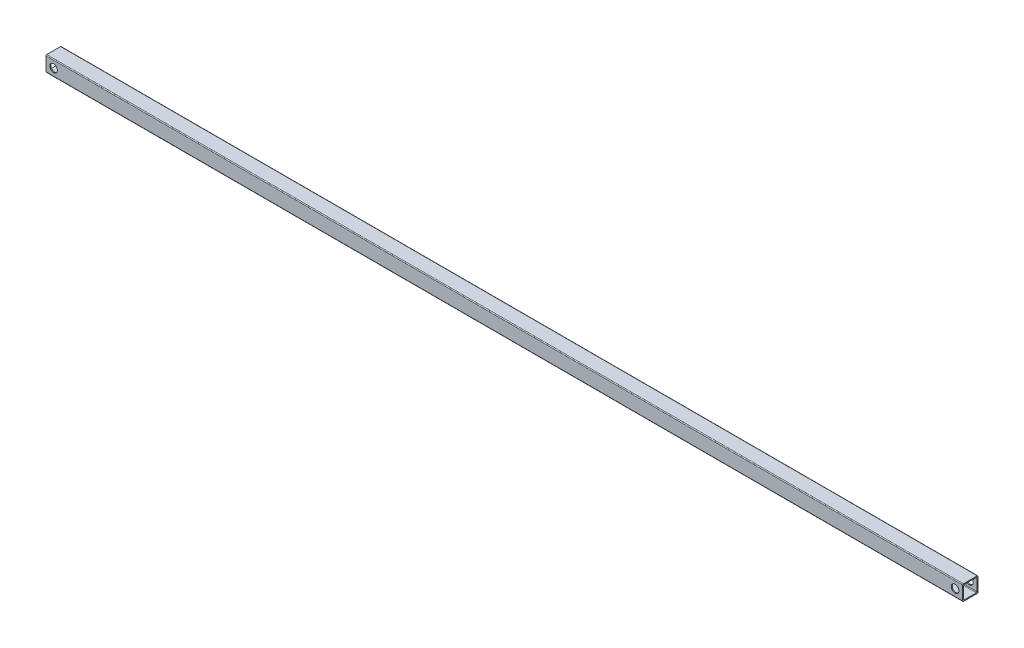
SolidWorks part; units mm, degrees
ref_plane "Front" through (0, 0, 0) normal (0, 0, 1) x (1, 0, 0)
ref_plane "Top" through (0, 0, 0) normal (0, 1, 0) x (1, 0, 0)
ref_plane "Right" through (0, 0, 0) normal (1, 0, 0) x (0, 0, -1)
sketch "Sketch1" plane through (0, 0, 0) normal (1, 0, 0) x (0, 0, -1)
  line L0 (-11.049, 0) -> (-12.7, 0) construction
  line L1 (11.43, -12.7) -> (-11.43, -12.7) construction
  line L2 (12.7, -11.43) -> (12.7, 11.43) construction
  line L3 (11.43, 12.7) -> (-11.43, 12.7) construction
  line L4 (-12.7, -11.43) -> (-12.7, 11.43) construction
  line L5 (12.7, -12.7) -> (-12.7, 12.7) construction
  line L6 (12.7, 12.7) -> (-12.7, -12.7) construction
  line L7 (9.9441, 11.049) -> (-9.9441, 11.049) construction
  line L8 (11.049, 9.9441) -> (11.049, -9.9441) construction
  line L9 (9.9441, -11.049) -> (-9.9441, -11.049) construction
  line L10 (-11.049, 9.9441) -> (-11.049, -9.9441) construction
  line L11 (11.049, 11.049) -> (-11.049, -11.049) construction
  line L12 (11.049, -11.049) -> (-11.049, 11.049) construction
  line L13 (0, -11.049) -> (0, -12.7) construction
  line L14 (11.049, -9.9441) -> (11.049, -12.7) construction
  line L15 (11.049, 0) -> (12.7, 0) construction
  line L16 (11.049, -12.7) -> (12.7, -12.7) construction
  arc A0 (-9.9441, -11.049) -> (-11.049, -9.9441) centre (-9.9441, -9.9441) cw construction
  arc A1 (11.049, -9.9441) -> (9.9441, -11.049) centre (9.9441, -9.9441) cw construction
  arc A2 (9.9441, 11.049) -> (11.049, 9.9441) centre (9.9441, 9.9441) cw construction
  arc A3 (-9.9441, 11.049) -> (-11.049, 9.9441) centre (-9.9441, 9.9441) ccw construction
  arc A4 (11.43, -12.7) -> (12.7, -11.43) centre (11.43, -11.43) ccw construction
  arc A5 (12.7, 11.43) -> (11.43, 12.7) centre (11.43, 11.43) ccw construction
  arc A6 (-11.43, 12.7) -> (-12.7, 11.43) centre (-11.43, 11.43) ccw construction
  arc A7 (-11.43, -12.7) -> (-12.7, -11.43) centre (-11.43, -11.43) cw construction
  point P0 (0, 0)
  point P6 (0, 0)
  dimension "D2" = 1.1049
  dimension "D3" = 1.27
  dimension "Outside Width" = 25.4
  dimension "Ouside Height" = 25.4
  dimension "Inside Height" = 22.098
  dimension "Wall Thickness" = 1.651
sketch "Sketch2" plane through (0, 0, 0) normal (0, 0, 1) x (1, 0, 0)
  line L0 (-762, 0) -> (762, 0) construction
  point P3 (-738.251, 0)
  point P4 (738.251, 0)
  dimension "Length" = 1524
  dimension "D1" = 23.749
  dimension "D2" = 23.749
sketch "Sketch4" plane through (0, 0, 0) normal (1, 0, 0) x (0, 0, -1)
  line L8 (12.7, -11.43) -> (12.7, 11.43)
  line L9 (11.43, 12.7) -> (-11.43, 12.7)
  line L10 (-12.7, -11.43) -> (-12.7, 11.43)
  line L11 (11.43, -12.7) -> (-11.43, -12.7)
  line L12 (11.049, 9.9441) -> (11.049, -9.9441)
  line L13 (9.9441, -11.049) -> (-9.9441, -11.049)
  line L14 (-11.049, 9.9441) -> (-11.049, -9.9441)
  line L15 (9.9441, 11.049) -> (-9.9441, 11.049)
  arc A8 (12.7, 11.43) -> (11.43, 12.7) centre (11.43, 11.43) ccw
  arc A9 (-11.43, 12.7) -> (-12.7, 11.43) centre (-11.43, 11.43) ccw
  arc A10 (-12.7, -11.43) -> (-11.43, -12.7) centre (-11.43, -11.43) ccw
  arc A11 (11.43, -12.7) -> (12.7, -11.43) centre (11.43, -11.43) ccw
  arc A12 (9.9441, -11.049) -> (11.049, -9.9441) centre (9.9441, -9.9441) ccw
  arc A13 (-11.049, -9.9441) -> (-9.9441, -11.049) centre (-9.9441, -9.9441) ccw
  arc A14 (-9.9441, 11.049) -> (-11.049, 9.9441) centre (-9.9441, 9.9441) ccw
  arc A15 (11.049, 9.9441) -> (9.9441, 11.049) centre (9.9441, 9.9441) ccw
extrude "Boss-Extrude1" add sketch "Sketch4" along normal up to vertex (-762 mm away) and the other way up to vertex (-762 mm away) up to point (-762, 0, 0) other way up to point (762, 0, 0)
sketch "Sketch6" plane through (0, 0, 12.7) normal (0, 0, 1) x (1, 0, 0)
  line L0 (762, 11.43) -> (762, -11.43) construction
  line L1 (762, 12.7) -> (-762, 12.7) construction
  line L2 (-762, 11.43) -> (-762, -11.43) construction
  circle A0 centre (749.3, 0) radius 6.35
  circle A1 centre (-749.3, 0) radius 6.35
  dimension "D1" = 12.7
  dimension "D2" = 12.7
  dimension "D3" = 12.7
  dimension "D4" = 12.7
  dimension "D5" = 12.7
  dimension "D6" = 12.7
extrude "Cut-Extrude1" cut sketch "Sketch6" against normal through all
equation "\"D3@Sketch1\"=\"Outside Width@Sketch1\"*.05"
equation "\"D2@Sketch1\" = \"Inside Height@Sketch1\" * .05"
equation "\"D1@Sketch2\"=\"Outside Width@Sketch1\"-\"Wall Thickness@Sketch1\""
equation "\"D2@Sketch2\"=\"D1@Sketch2\""
